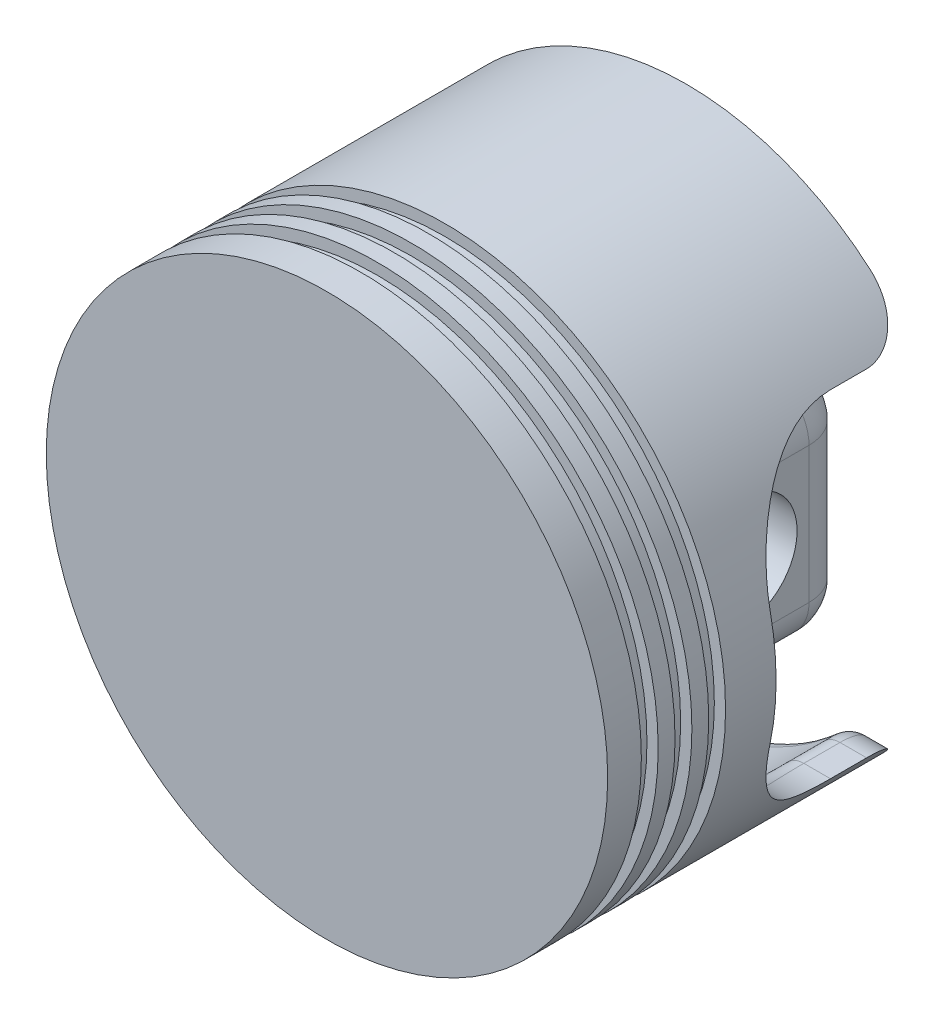
SolidWorks part; units mm, degrees
ref_plane "Front Plane" through (0, 0, 0) normal (1, 0, 0) x (0, 1, 0)
ref_plane "Top Plane" through (0, 0, 0) normal (0, 0, 1) x (0, 1, 0)
ref_plane "Right Plane" through (0, 0, 0) normal (0, 1, 0) x (-1, 0, 0)
sketch "Sketch1" plane through (0, 0, 0) normal (1, 0, 0) x (0, 1, 0)
  line L0 (0, 0) -> (63.5, 0)
  line L1 (63.5, 0) -> (63.5, -81.28)
  line L2 (63.5, -81.28) -> (57.15, -81.28)
  line L3 (57.15, -81.28) -> (57.15, -19)
  line L4 (57.15, -19) -> (0, -19)
  line L5 (0, -19) -> (0, 0)
  dimension "D1" = 19
  dimension "D2" = 63.5
  dimension "D3" = 6.35
  dimension "D4" = 81.28
revolve "Revolve1" add sketch "Sketch1" angle 360 about L5
sketch "Sketch2" plane through (0, 0, 0) normal (1, 0, 0) x (0, 1, 0)
  line L0 (63.5, -7.62) -> (60.96, -7.62)
  line L1 (60.96, -7.62) -> (60.96, -11.43)
  line L2 (60.96, -11.43) -> (63.5, -11.43)
  line L3 (63.5, -7.62) -> (63.5, -11.43)
  line L4 (63.5, 0) -> (-63.5, 0) construction
  point P6 (63.5, -9.525)
  dimension "D1" = 7.62
  dimension "D2" = 3.81
  dimension "D3" = 2.54
  dimension "D4" = 63.5
ref_axis "Axis1" through (0, 0, 32.4855) along (0, 0, -1)
revolve "Cut-Revolve1" cut sketch "Sketch2" angle 360 about axis through (0, 0, 32.4855) along (0, 0, -1)
pattern_linear "LPattern1" count 3 spacing 7.62 along (0, 0, -1) of "Cut-Revolve1"
sketch "Sketch3" plane through (0, 0, 0) normal (1, 0, 0) x (0, 1, 0)
  line L0 (0, 32.4855) -> (0, -108.8847) construction
  line L1 (-38.1, -38.1) -> (38.1, -38.1)
  line L2 (-38.1, -38.1) -> (-38.1, -81.28)
  line L3 (-38.1, -81.28) -> (38.1, -81.28)
  line L4 (38.1, -38.1) -> (38.1, -81.28)
  line L5 (-38.1, -38.1) -> (38.1, -81.28) construction
  line L6 (-38.1, -81.28) -> (38.1, -38.1) construction
  line L7 (63.5, 0) -> (-63.5, 0) construction
  line L8 (-57.15, -81.28) -> (57.15, -81.28) construction
  point P0 (0, -59.69)
  dimension "D1" = 38.1
  dimension "D2" = 76.2
extrude "Cut-Extrude1" cut sketch "Sketch3" against normal through all both and the other way through all
fillet "Fillet2" radius 25 4 edges at (46.6985, -38.1, -38.1) (46.6985, 38.1, -38.1) (-46.6985, -38.1, -38.1) (-46.6985, 38.1, -38.1)
fillet "Fillet3" radius 10 4 edges at (-46.6985, -38.1, -81.28) (46.6985, -38.1, -81.28) (46.6985, 38.1, -81.28) (-46.6985, 38.1, -81.28)
sketch "Sketch4" plane through (0, 0, -19) normal (0, 0, -1) x (1, 0, 0)
  line L1 (-36.55, 25.4) -> (-17.55, 25.4)
  line L2 (-36.55, 25.4) -> (-36.55, -25.4)
  line L3 (-36.55, -25.4) -> (-17.55, -25.4)
  line L4 (-17.55, 25.4) -> (-17.55, -25.4)
  line L5 (-36.55, 25.4) -> (-17.55, -25.4) construction
  line L6 (-36.55, -25.4) -> (-17.55, 25.4) construction
  point P0 (-27.05, 0)
  point P6 (0, 0)
  dimension "D1" = 19
  dimension "D2" = 50.8
  dimension "D3" = 17.55
extrude "Boss-Extrude1" add sketch "Sketch4" along normal blind 63.5
mirror "Mirror1" about plane through (0, 0, 0) normal (1, 0, 0) of "Boss-Extrude1"
fillet "Fillet4" radius 10 4 edges at (27.05, 25.4, -82.5) (27.05, -25.4, -82.5) (-27.05, 25.4, -82.5) (-27.05, -25.4, -82.5)
fillet "Fillet11" radius 10 10 edges at (-17.55, 25.4, -45.75) (-17.55, 22.4711, -79.5711) (-17.55, -25.4, -45.75) (-17.55, -22.4711, -79.5711) (-17.55, 0, -82.5) (36.55, -25.4, -45.75) (36.55, -22.4711, -79.5711) (36.55, 25.4, -45.75) (36.55, 22.4711, -79.5711) (36.55, 0, -82.5)
fillet "Fillet12" radius 10 10 edges at (17.55, 25.4, -45.75) (17.55, 22.4711, -79.5711) (17.55, -25.4, -45.75) (17.55, -22.4711, -79.5711) (17.55, 0, -82.5) (-36.55, -25.4, -45.75) (-36.55, -22.4711, -79.5711) (-36.55, 25.4, -45.75) (-36.55, 22.4711, -79.5711) (-36.55, 0, -82.5)
sketch "Sketch5" plane through (36.55, 0, 0) normal (1, 0, 0) x (0, 1, 0)
  line L0 (0, 32.4855) -> (0, -108.8847) construction
  line L1 (15.4, -82.5) -> (-15.4, -82.5) construction
  circle A0 centre (0, -57.1) radius 12.7
  dimension "D1" = 25.4
  dimension "D2" = 25.4
extrude "Cut-Extrude2" cut sketch "Sketch5" against normal through all both and the other way through all
fillet "Fillet15" radius 5 16 edges at (41.3657, -39.4335, -76.2692) (42.5971, -38.1, -67.19) (49.5699, -28.4419, -43.3611) (57.15, 0, -38.1) (45.69, 34.33, -49.8982) (42.5971, 38.1, -67.19) (40.0022, 40.816, -78.1316) (0, 57.15, -81.28) (-41.3657, 39.4335, -76.2692) (-42.5971, 38.1, -67.19) (-49.5699, 28.4419, -43.3611) (-57.15, 0, -38.1) (-45.69, -34.33, -49.8982) (-42.5971, -38.1, -67.19) (-40.0022, -40.816, -78.1316) (0, -57.15, -81.28)
fillet "Fillet16" radius 5 1 edges at (-57.15, 0, -19)
